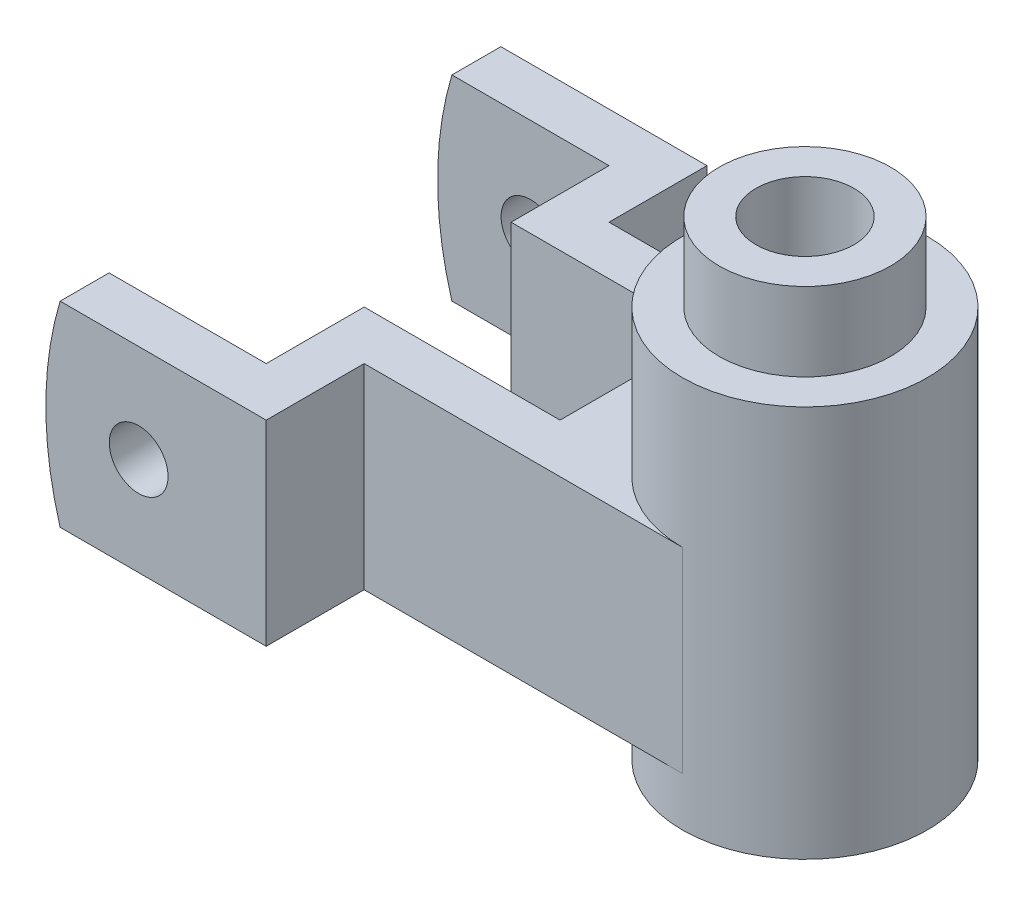
SolidWorks part; units mm, degrees
ref_plane "Front Plane" through (0, 0, 0) normal (0, 0, 1) x (1, 0, 0)
ref_plane "Top Plane" through (0, 0, 0) normal (0, 1, 0) x (1, 0, 0)
ref_plane "Right Plane" through (0, 0, 0) normal (1, 0, 0) x (0, 0, -1)
sketch "Sketch1" plane through (0, 0, 0) normal (0, 1, 0) x (1, 0, 0)
  line L0 (-56.2735, 36.0169) -> (-56.2735, 26.0169)
  line L1 (-56.2735, 36.0169) -> (-11.2735, 36.0169)
  line L2 (-21.2735, 26.0169) -> (-21.2735, 6.0169)
  line L3 (-21.2735, 6.0169) -> (18.7265, 6.0169)
  line L4 (-56.2735, 26.0169) -> (-21.2735, 26.0169)
  line L5 (18.7265, 6.0169) -> (18.7265, -23.9831)
  line L6 (18.7265, -23.9831) -> (-21.2735, -23.9831)
  line L7 (-11.2735, 36.0169) -> (-11.2735, 16.0169)
  line L8 (-11.2735, 16.0169) -> (53.7265, 16.0169)
  line L9 (-21.2735, -23.9831) -> (-21.2735, -43.9831)
  line L10 (-21.2735, -43.9831) -> (-56.2735, -43.9831)
  line L11 (-56.2735, -43.9831) -> (-56.2735, -53.9831)
  line L12 (-56.2735, -53.9831) -> (-11.2735, -53.9831)
  line L13 (-11.2735, -53.9831) -> (-11.2735, -33.9831)
  line L14 (-11.2735, -33.9831) -> (53.7265, -33.9831)
  line L15 (53.7265, 16.0169) -> (53.7265, -33.9831)
extrude "Boss-Extrude1" add sketch "Sketch1" along normal blind 40
sketch "Sketch2" plane through (0, 0, 53.9831) normal (0, 0, 1) x (1, 0, 0)
  line L0 (-53.3556, 40) -> (-56.2735, 40)
  line L1 (-56.2735, 40) -> (-56.2735, 0) construction
  line L2 (-56.2735, 40) -> (-56.2735, 20)
  line L3 (-53.3556, 0) -> (-56.2735, 0)
  line L4 (-56.2735, 0) -> (-56.2735, 20)
  line L8 (-56.2735, 40) -> (-11.2735, 40) construction
  line L9 (55, 0) -> (-55, 0) construction
  arc A3 (-53.3556, 40) -> (-53.3556, 0) centre (13.7265, 20) ccw
  line M9 (-56.2735, 0) -> (-11.2735, 0)
  line M11 (-11.2735, 40) -> (-56.2735, 40)
  line M12 (-56.2735, 40) -> (-56.2735, 0)
extrude "Cut-Extrude2" cut sketch "Sketch2" against normal blind 90 contours A3 M12 M9 | A3 M11 M12 region at (-55.4013, 35.0211, 53.9831) region at (-55.4013, 4.9789, 53.9831)
sketch "Sketch3" plane through (0, 0, -26.0169) normal (0, 0, 1) x (1, 0, 0)
  circle A0 centre (-37.3145, 20) radius 6
sketch "Sketch4" plane through (0, 0, -26.0169) normal (0, 0, 1) x (1, 0, 0)
extrude "Cut-Extrude4" cut sketch "Sketch3" against normal blind 151 and the other way blind 151
sketch3d "3DSketch1"
  line L0 (53.7265, 40, 33.9831) -> (53.7265, 40, -16.0169) construction
  circle A0 centre (53.7265, 40, 8.9831) radius 25
  point P2 (53.7265, 65, 8.9831)
extrude "Boss-Extrude2" add sketch "3DSketch1" along direction (0, 1, 0) on the side of the normal blind 30 and the other way blind 50
sketch "Sketch5" plane through (0, 0, 0) normal (0, 1, 0) x (1, 0, 0)
  circle A3 centre (53.7265, -8.9831) radius 17.5
  circle A4 centre (53.7265, -8.9831) radius 10
extrude "Boss-Extrude3" add sketch "Sketch5" along normal blind 86
